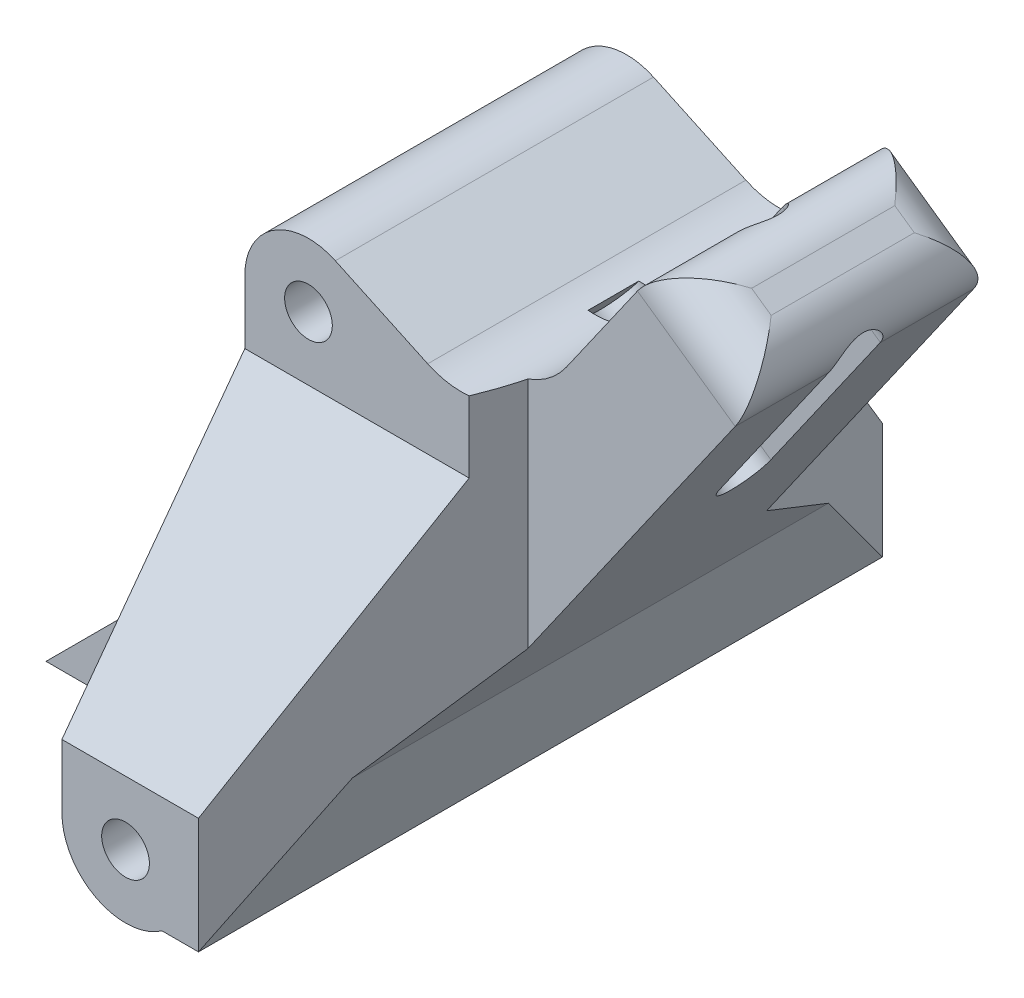
SolidWorks part; units mm, degrees
material "ABS"
ref_plane "Front Plane" through (0, 0, 0) normal (0, 0, 1) x (1, 0, 0)
ref_plane "Top Plane" through (0, 0, 0) normal (0, 1, 0) x (1, 0, 0)
ref_plane "Right Plane" through (0, 0, 0) normal (1, 0, 0) x (0, 0, -1)
sketch "background-img"
sketch "Sketch2" plane through (0, 0, 0) normal (0, 0, 1) x (1, 0, 0)
  line L1 (26.046, 30.6597) -> (19.9024, 34.9615)
  line L4 (-4, 23.5294) -> (-4, 0)
  line L6 (0, 0) -> (44.6065, 0) construction
  line L7 (1.6905, 27.1546) -> (11.2988, 22.6742)
  line L8 (11.2988, 22.6742) -> (19.9024, 34.9615)
  line L10 (4.5855, -3.2766) -> (7.722, 4.4903)
  line L11 (0, 0) -> (0, 23.5294) construction
  line L13 (4.3534, 6.2173) -> (22.9742, 32.8106) construction
  line L14 (0, 23.5294) -> (0, 27.5294) construction
  line L15 (2.2943, -3.2766) -> (0, 0) construction
  line L16 (7.722, 4.4903) -> (26.046, 30.6597)
  line L17 (4.5855, -3.2766) -> (2.2943, -3.2766)
  circle A0 centre (0, 0) radius 1.5
  arc A1 (-4, 0) -> (2.2943, -3.2766) centre (0, 0) ccw
  circle A2 centre (0, 23.5294) radius 1.5
  arc A3 (1.6905, 27.1546) -> (-4, 23.5294) centre (0, 23.5294) ccw
  dimension "D2" = 3
  dimension "D3" = 8
  dimension "D1" = 23.5294
  dimension "D4" = 100
  dimension "D5" = 35
  dimension "D6" = 35
  dimension "D7" = 15
  dimension "D8" = 7.5
extrude "main-extrude" add sketch "Sketch2" along normal mid plane 43 contours L7 A3 L4 A1 L16 L1 L8 A0 A2 region at (7.018, 15.792, 0)
ref_plane "horizontal-cut-plane" through (0, 27.5294, 0) normal (0, 1, 0) x (1, 0, 0)
sketch "Sketch5" plane through (0, 27.5294, 0) normal (0, -1, 0) x (-1, 0, 0)
  line L0 (-4.5855, -21.5) -> (-4.5855, 21.5) construction
  line L2 (-4.5855, -21.5) -> (-4.5855, 21.5) construction
  line L4 (-1.6905, -21.5) -> (4, -21.5) construction
  line L6 (-26.046, -21.5) -> (-26.046, 21.5) construction
  line L16 (4, 0) -> (-26.046, 0) construction
  line L17 (-4.5855, 21.5) -> (-11.2988, 7.5)
  line L18 (-11.2988, -21.5) -> (-11.2988, 21.5) construction
  line L19 (-11.2988, 7.5) -> (-26.046, 7.5)
  line L22 (-11.2988, -7.5) -> (-26.046, -7.5)
  line L23 (-4.5855, -21.5) -> (-11.2988, -7.5)
  line L24 (4, -21.5) -> (4, 21.5) construction
  line L33 (4, -21.5) -> (4, 21.5)
  line L34 (-11.2988, -21.5) -> (-11.2988, 21.5) construction
  line L35 (-1.6905, -21.5) -> (-11.2988, -21.5) construction
  line L36 (-1.6905, -21.5) -> (4, -21.5)
  line L37 (-26.046, -7.5) -> (-26.046, 7.5)
  line L38 (-1.6905, -21.5) -> (-4.5855, -21.5)
  line L39 (-1.6905, 21.5) -> (-11.2988, 21.5) construction
  line L40 (4, 21.5) -> (-1.6905, 21.5) construction
  line L41 (-1.6905, 21.5) -> (-4.5855, 21.5)
  line L42 (4, 21.5) -> (-1.6905, 21.5)
  point P3 (0, 0)
  point P21 (0, 0)
  dimension "D1" = 15
extrude "horizontal-cut" cut sketch "Sketch5" against normal through all both and the other way through all flip side to cut
sketch "Sketch15" plane through (-4, 0, 0) normal (-1, 0, 0) x (0, 0, 1)
  line L0 (-21.5, 0) -> (-21.5, -4) construction
  line L1 (21.5, -4) -> (21.5, 0) construction
  line L2 (7.5, 34.9615) -> (-7.5, 34.9615) construction
  line L5 (-21.5, -4) -> (21.5, -4) construction
  line L6 (-10, 34.9615) -> (10, 34.9615)
  line L8 (7.5, 34.9615) -> (-7.5, 34.9615) construction
  line L11 (-21.5, -4) -> (21.5, -4)
  line L12 (0, 34.9615) -> (0, -4) construction
  line L14 (21.5, 0) -> (-21.5, 0) construction
  line L15 (21.5, 0) -> (-21.5, 0) construction
  line L16 (21.5, 4) -> (21.5, 0)
  line L17 (-21.5, 0) -> (-21.5, -4)
  line L20 (21.5, 23.5294) -> (-21.5, 23.5294) construction
  line L21 (21.5, 23.5294) -> (-21.5, 23.5294) construction
  line L24 (21.5, 27.5294) -> (-21.5, 27.5294) construction
  line L25 (21.5, -4) -> (21.5, 0)
  line L28 (-21.5, 19.5294) -> (21.5, 19.5294) construction
  line L29 (-10, 34.9615) -> (-10, 19.5294)
  line L30 (-10, 19.5294) -> (-21.5, 4)
  line L31 (10, 34.9615) -> (10, 19.5294)
  line L32 (10, 19.5294) -> (21.5, 4)
  line L33 (-21.5, 23.5294) -> (-21.5, 0)
  line L34 (-21.5, 0) -> (21.5, 0)
  line L35 (21.5, 0) -> (21.5, 23.5294)
  line L36 (21.5, 23.5294) -> (-21.5, 23.5294)
  line L38 (-21.5, 0) -> (21.5, 0) construction
  line L39 (21.5, 0) -> (21.5, 4)
  line L40 (21.5, 23.5294) -> (-21.5, 23.5294) construction
  line L41 (-21.5, 4) -> (-21.5, 0)
  line L42 (21.5, 27.5294) -> (-21.5, 27.5294) construction
  line L43 (21.5, 23.5294) -> (21.5, 0) construction
  point P11 (0, 34.9615)
  point P15 (10, 19.5096)
  point P20 (21.5, 19.4854)
  line M4 (-21.5, 0) -> (21.5, 0)
  line M6 (21.5, 23.5294) -> (-21.5, 23.5294)
  line M27 (-21.5, 23.5294) -> (-21.5, 0)
  line M28 (21.5, 0) -> (21.5, 23.5294)
  dimension "D1" = 20
  dimension "D3" = 8
  dimension "D2" = 0
extrude "vertical-cut" cut sketch "Sketch15" against normal through all both and the other way through all flip side to cut contours L32 L31 L29 L30 M6 M27 M4 M28 | L31 L6 L29 M6 | L11 L25 L17 M4 region at (-4, 29.2455, 0) region at (-4, 9.929, 0) region at (-4, -2, 0)
fillet "end-fillet" radius 3 4 edges at (19.9024, 34.9615, 0) (26.046, 30.6597, 0) (22.9742, 32.8106, 7.5) (22.9742, 32.8106, -7.5)
sketch "Sketch13" plane through (0, 0, 0) normal (0, 0, 1) x (1, 0, 0)
  line L2 (-4, 2.75) -> (0, 2.75)
  line L3 (2.75, 0) -> (2.75, -3.2766)
  line L5 (2.75, -3.2766) -> (2.2943, -3.2766)
  line L6 (-4, 2.75) -> (-10, 2.75)
  line L7 (-10, 2.75) -> (-4, 8.75)
  line L9 (-4, 4) -> (-4, 0) construction
  line L10 (-4, 2.75) -> (-4, 0)
  line L11 (-4, 2.75) -> (-4, 8.75)
  line L12 (4.5855, -3.2766) -> (2.2943, -3.2766) construction
  line L13 (2.75, -3.2766) -> (2.2943, -3.2766)
  arc A3 (2.75, 0) -> (0, 2.75) centre (0, 0) ccw
  arc A7 (-4, 0) -> (2.2943, -3.2766) centre (0, 0) ccw construction
  arc A8 (-4, 0) -> (2.2943, -3.2766) centre (0, 0) ccw
  circle A11 centre (0, 0) radius 1.5 construction
  circle A12 centre (0, 0) radius 1.5 construction
  point P4 (0, 0)
  point P16 (2.8099, -0.0123)
  point P18 (3.721, -2.8787)
  point P20 (2.75, -3.2766)
  point P21 (0, 0)
  dimension "D1" = 1.25
  dimension "D2" = 6
  dimension "D3" = 45
extrude "spring-place-cut" cut sketch "Sketch13" against normal mid plane 34 contours L3 A3 L2 L5 region at (-0.5809, -0.4556, 0)
extrude "spring-back-support" add sketch "Sketch13<4>" along normal mid plane 33 contours L6 L7 region at (-6, 4.75, 0)
sketch "Sketch13<4>" plane through (0, 0, 0) normal (0, 0, 1) x (1, 0, 0) same geometry as "Sketch13"
fillet "Fillet4" radius 5 1 edges at (11.2988, 22.6742, 0)
sketch "Sketch12" plane through (3.0718, -2.1509, 0) normal (0.8192, -0.5736, 0) x (0, 0, -1)
  line L1 (-1.6, 37.0984) -> (-1.6, 25.0984)
  line L2 (1.6, 37.0984) -> (1.6, 25.0984)
  arc A0 (1.6, 37.0984) -> (-1.6, 37.0984) centre (0, 37.0984) ccw
  arc A1 (-1.6, 25.0984) -> (1.6, 25.0984) centre (0, 25.0984) ccw
  dimension "D2" = 12
extrude "pusher-screw-hole" cut sketch "Sketch12" against normal blind 10
